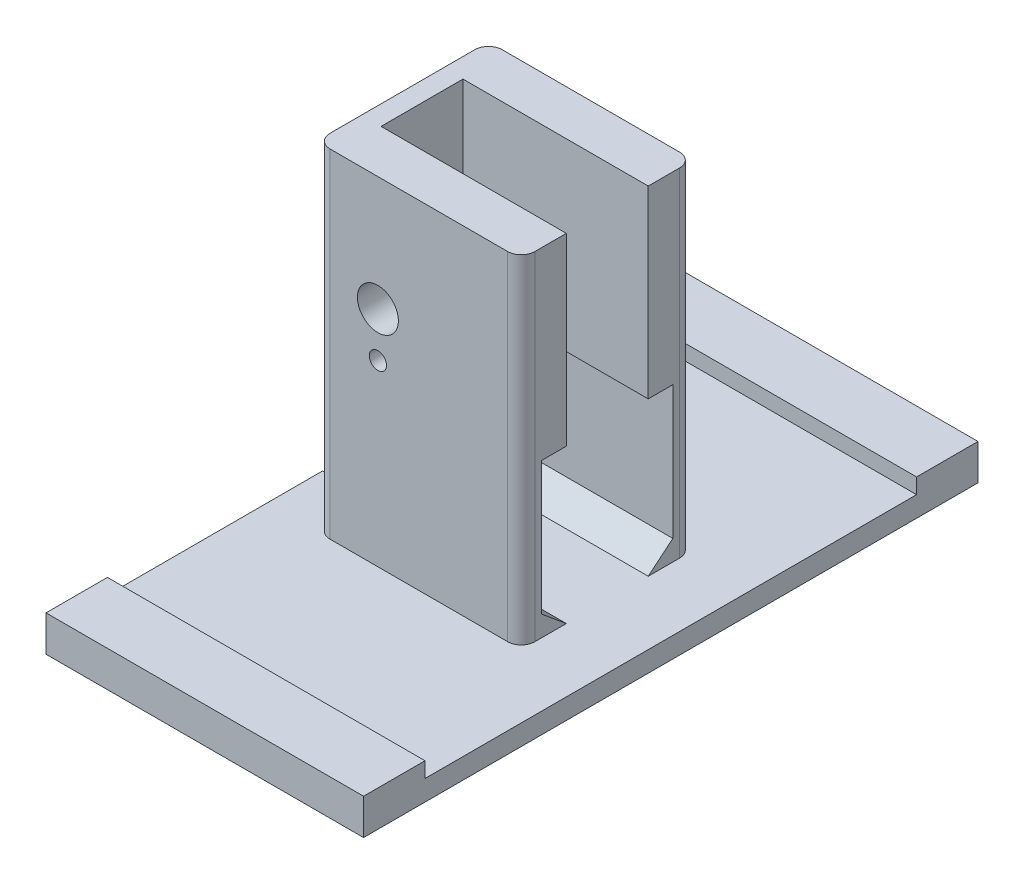
SolidWorks part; units mm, degrees
ref_plane "Front Plane" through (0, 0, 0) normal (0, 0, 1) x (1, 0, 0)
ref_plane "Top Plane" through (0, 0, 0) normal (0, 1, 0) x (1, 0, 0)
ref_plane "Right Plane" through (0, 0, 0) normal (1, 0, 0) x (0, 0, -1)
sketch "Sketch2" plane through (0, 0, 0) normal (0, 1, 0) x (1, 0, 0)
  line L0 (0, 38.1) -> (39.3827, 38.1) construction
  line L1 (0, 0) -> (39.3827, 0)
  line L2 (0, 0) -> (0, 76.2)
  line L3 (0, 76.2) -> (39.3827, 76.2)
  line L4 (39.3827, 0) -> (39.3827, 76.2)
  line L7 (39.3827, 68.58) -> (0, 68.58)
  line L8 (8.5334, 38.1) -> (8.5334, 33.02)
  line L9 (8.5334, 33.02) -> (16.1534, 33.02)
  line L10 (8.5334, 38.1) -> (8.5334, 43.18)
  line L11 (8.5334, 43.18) -> (16.1534, 43.18)
  line L12 (16.1534, 43.18) -> (16.1534, 33.02)
  line L13 (33.1404, 76.2) -> (33.1404, 68.58) construction
  line L14 (28.6413, 0) -> (28.6413, 7.62) construction
  line L15 (39.3827, 7.62) -> (0, 7.62)
  line L16 (6.1079, 38.1) -> (6.1079, 27.432)
  line L17 (6.1079, 27.432) -> (31.5079, 27.432)
  line L18 (6.1079, 38.1) -> (6.1079, 48.768)
  line L19 (6.1079, 48.768) -> (31.5079, 48.768)
  line L20 (31.5079, 48.768) -> (31.5079, 27.432)
  line L21 (16.1534, 43.18) -> (31.5079, 43.18)
  line L22 (16.1534, 33.02) -> (31.5079, 33.02)
  arc A2 (0, 41.91) -> (0, 34.29) centre (0, 38.1) cw
  dimension "D1" = 5.588
  dimension "D2" = 76.2
  dimension "D3" = 39.3827
  dimension "D4" = 10.16
  dimension "D5" = 25.4
  dimension "D6" = 7.62
extrude "Boss-Extrude2" add sketch "Sketch2" along normal blind 4.445 contours L4 L15 L2 L1 | L7 L4 L3 L2 region at (19.6913, 0, -3.81) region at (19.6913, 0, -72.39)
extrude "Boss-Extrude3" add sketch "Sketch2<3>" along normal blind 2.54 contours L15 L4 L7 L2 | L20 L19 L18 L16 L17 L11 L12 L9 L8 L10 | L12 L11 L10 L8 L9 | L9 | L11 | L12 L22 L20 L21 region at (0.7257, 0, -20.955) region at (12.3434, 0, -38.1) region at (8.2017, 0, -35.56) region at (23.8306, 0, -38.1)
sketch "Sketch2<3>" plane through (0, 0, 0) normal (0, 1, 0) x (1, 0, 0) same geometry as "Sketch2"
extrude "Boss-Extrude4" add sketch "Sketch2<8>" along normal blind 44.45 contours L20 L19 L18 L16 L17 L8 L10 L12 | L11 | L9 region at (8.2017, 0, -35.56)
sketch "Sketch2<8>" plane through (0, 0, 0) normal (0, 1, 0) x (1, 0, 0) same geometry as "Sketch2"
sketch "Sketch5" plane through (0, 0, -48.768) normal (0, 0, -1) x (-1, 0, 0)
  line L0 (-13.7279, 30.226) -> (-31.5079, 30.226) construction
  line L3 (-13.7279, 30.226) -> (-13.7279, 24.6888) construction
  line L4 (-31.5079, 44.45) -> (-6.1079, 44.45) construction
  line L5 (-31.5079, 44.45) -> (-31.5079, 2.54) construction
  line L6 (-13.7279, 30.226) -> (-6.1079, 30.226) construction
  line L7 (-6.1079, 44.45) -> (-6.1079, 2.54) construction
  circle A0 centre (-13.7279, 30.226) radius 2.54
  circle A1 centre (-13.7279, 24.6888) radius 1.0668
  dimension "D1" = 14.224
  dimension "D2" = 7.62
  dimension "D3" = 5.5372
extrude "Cut-Extrude3" cut sketch "Sketch5" against normal up to surface (21.336 mm away) up to face at (18.8079, 23.495, -27.432)
sketch "Sketch6" plane through (0, 44.45, 0) normal (0, 1, 0) x (1, 0, 0)
  line L0 (29.8145, 27.432) -> (29.8145, 29.1253) construction
  line L1 (6.1079, 27.432) -> (31.5079, 27.432) construction
  line L2 (29.8145, 29.1253) -> (31.5079, 29.1253) construction
  line L3 (31.5079, 48.768) -> (31.5079, 43.18) construction
  line L4 (31.5079, 29.1253) -> (31.5079, 27.432)
  line L5 (31.5079, 27.432) -> (29.8145, 27.432)
  line L6 (6.1079, 29.1253) -> (7.8012, 29.1253) construction
  line L7 (6.1079, 27.432) -> (6.1079, 48.768) construction
  line L8 (7.8012, 29.1253) -> (7.8012, 27.432) construction
  line L9 (7.8012, 48.768) -> (7.8012, 47.0747) construction
  line L10 (29.8145, 48.768) -> (29.8145, 47.0747) construction
  line L11 (6.1079, 48.768) -> (31.5079, 48.768) construction
  line L12 (29.8145, 47.0747) -> (31.5079, 47.0747) construction
  line L13 (7.8012, 47.0747) -> (6.1079, 47.0747) construction
  line L14 (7.8012, 48.768) -> (6.1079, 48.768)
  line L15 (6.1079, 48.768) -> (6.1079, 47.0747)
  line L16 (6.1079, 29.1253) -> (6.1079, 27.432)
  line L17 (6.1079, 27.432) -> (7.8012, 27.432)
  line L18 (29.8145, 48.768) -> (31.5079, 48.768)
  line L19 (31.5079, 48.768) -> (31.5079, 47.0747)
  arc A0 (31.5079, 29.1253) -> (29.8145, 27.432) centre (29.8145, 29.1253) cw
  arc A1 (7.8012, 48.768) -> (6.1079, 47.0747) centre (7.8012, 47.0747) ccw
  arc A2 (7.8012, 27.432) -> (6.1079, 29.1253) centre (7.8012, 29.1253) cw
  arc A3 (29.8145, 48.768) -> (31.5079, 47.0747) centre (29.8145, 47.0747) cw
  line M5 (31.5079, 27.432) -> (31.5079, 33.02)
  line M6 (31.5079, 48.768) -> (6.1079, 48.768)
  line M7 (6.1079, 48.768) -> (6.1079, 27.432)
  line M8 (6.1079, 27.432) -> (31.5079, 27.432)
extrude "Cut-Extrude5" cut sketch "Sketch6" against normal up to surface (41.91 mm away) contours A1 M6 M7 | A3 M6 M5 | A2 M8 M7 | A0 M5 M8 region at (31.1296, 44.45, -48.3898) region at (6.4861, 44.45, -48.3898) region at (6.4861, 44.45, -27.8102) region at (31.1296, 44.45, -27.8102) up to face at (19.4142, 2.54, -38.1)
sketch "Sketch7" plane through (0, 2.54, 0) normal (0, 1, 0) x (1, 0, 0)
  line L0 (31.5079, 43.18) -> (8.5334, 43.18)
  line L1 (8.5334, 46.228) -> (31.5079, 46.228)
  line L2 (31.5079, 46.228) -> (31.5079, 43.18)
  line L3 (8.5334, 43.18) -> (8.5334, 46.228)
  line L4 (31.5079, 33.02) -> (8.5334, 33.02)
  line L5 (8.5334, 33.02) -> (8.5334, 43.18) construction
  line L6 (31.5079, 33.02) -> (8.5334, 33.02) construction
  line L7 (8.5334, 33.02) -> (8.5334, 29.972)
  line L8 (8.5334, 29.972) -> (31.5079, 29.972)
  line L9 (31.5079, 29.972) -> (31.5079, 33.02)
extrude "Cut-Extrude7" cut sketch "Sketch7" along normal blind 16.51 from offset 2.54
sketch "Sketch8" plane through (31.5079, 0, 0) normal (1, 0, 0) x (0, 0, -1)
  line L0 (33.02, 2.54) -> (29.972, 5.08)
  line L1 (29.972, 5.08) -> (33.02, 5.08)
  line L2 (33.02, 5.08) -> (33.02, 2.54)
  line L3 (43.18, 2.54) -> (46.228, 5.08)
  line L4 (46.228, 5.08) -> (43.18, 5.08)
  line L5 (43.18, 5.08) -> (43.18, 2.54)
extrude "Cut-Extrude8" cut sketch "Sketch8" against normal up to surface (22.9744 mm away) up to face at (8.5334, 16.7217, -38.1)
